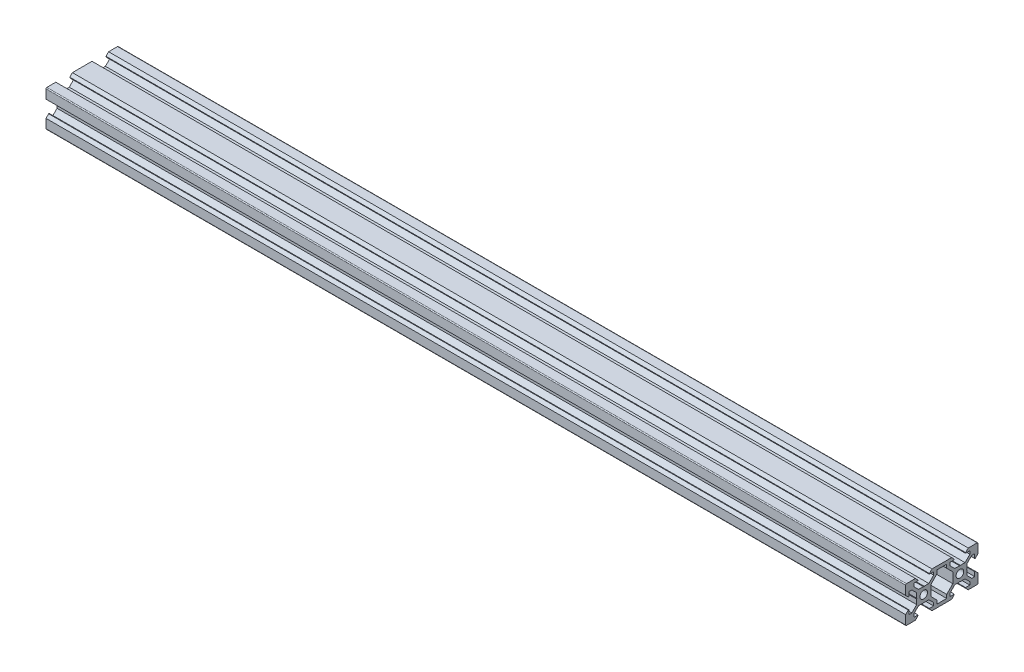
SolidWorks part; units mm, degrees
material "6061-T6 (SS)"
ref_plane "Top" through (0, 0, 0) normal (0, 0, 1) x (1, 0, 0)
ref_plane "Front" through (0, 0, 0) normal (0, 1, 0) x (1, 0, 0)
ref_plane "Right" through (0, 0, 0) normal (1, 0, 0) x (0, 0, -1)
sketch "Profile Sketch" plane through (0, 0, 0) normal (1, 0, 0) x (0, 0, -1)
  line L0 (5.42, 10) -> (-5.42, 10)
  line L1 (-4.5, 8.2) -> (-4.5, 6.56)
  line L2 (-4.5, 6.56) -> (-7.16, 3.9)
  line L3 (-7.16, 3.9) -> (-9.79, 3.9)
  line L4 (-9.79, 3.9) -> (-10, 3.69)
  line L5 (2.7, 8.2) -> (-2.7, 8.2)
  line L6 (-2.7, 8.2) -> (-2.7, 6.2387)
  line L7 (-2.7, 6.2387) -> (-6.1, 2.8387)
  line L8 (-6.1, 2.8387) -> (-6.1, -0.21)
  line L9 (-6.875, 8.545) -> (-6.875, 8.2)
  line L10 (-6.875, 8.2) -> (-4.5, 8.2)
  line L11 (-6.875, 8.545) -> (-5.42, 10)
  line L12 (0, -10) -> (0, 10) construction
  line L13 (-20, 0) -> (20, 0) construction
  line L14 (-10, -10) -> (-10, 10) construction
  line L15 (-6.875, -8.545) -> (-5.42, -10)
  line L16 (-6.875, -8.2) -> (-4.5, -8.2)
  line L17 (-6.875, -8.545) -> (-6.875, -8.2)
  line L18 (-2.7, -6.2387) -> (-6.1, -2.8387)
  line L19 (-2.7, -8.2) -> (-2.7, -6.2387)
  line L20 (2.7, -8.2) -> (-2.7, -8.2)
  line L21 (-7.16, -3.9) -> (-9.79, -3.9)
  line L22 (-4.5, -6.56) -> (-7.16, -3.9)
  line L23 (-4.5, -8.2) -> (-4.5, -6.56)
  line L24 (5.42, -10) -> (-5.42, -10)
  line L25 (-10, 0) -> (-20, 10) construction
  line L26 (-18.545, 3.125) -> (-18.2, 3.125)
  line L27 (-13.125, -8.545) -> (-13.125, -8.2)
  line L28 (-13.125, -8.2) -> (-15.5, -8.2)
  line L29 (-13.125, -8.545) -> (-14.58, -10)
  line L30 (-15.5, -8.2) -> (-15.5, -6.56)
  line L31 (-15.5, -6.56) -> (-12.84, -3.9)
  line L32 (-12.84, -3.9) -> (-10.21, -3.9)
  line L33 (-20, 4.58) -> (-20, 9.5)
  line L34 (-13.9, 2.8387) -> (-13.9, 0.21)
  line L35 (-16.56, 5.5) -> (-13.9, 2.8387)
  line L36 (-12.84, 3.9) -> (-10.21, 3.9)
  line L37 (-15.5, 6.56) -> (-12.84, 3.9)
  line L38 (-15.5, 8.2) -> (-15.5, 6.56)
  line L39 (-13.125, 8.545) -> (-14.58, 10)
  line L40 (-13.125, 8.2) -> (-15.5, 8.2)
  line L41 (-13.125, 8.545) -> (-13.125, 8.2)
  line L42 (-18.2, 3.125) -> (-18.2, 5.5)
  line L43 (-18.545, 3.125) -> (-20, 4.58)
  line L44 (-18.2, 5.5) -> (-16.56, 5.5)
  line L45 (-14.58, 10) -> (-19.5, 10)
  line L46 (-16.56, -5.5) -> (-13.9, -2.8387)
  line L47 (-14.58, -10) -> (-19.5, -10)
  line L48 (-18.2, -5.5) -> (-16.56, -5.5)
  line L49 (-18.545, -3.125) -> (-20, -4.58)
  line L50 (-18.2, -3.125) -> (-18.2, -5.5)
  line L51 (-20, -4.58) -> (-20, -9.5)
  line L52 (-18.545, -3.125) -> (-18.2, -3.125)
  line L53 (10, -10) -> (10, 10) construction
  line L54 (18.545, -3.125) -> (18.2, -3.125)
  line L55 (20, -4.58) -> (20, -9.5)
  line L56 (18.2, -3.125) -> (18.2, -5.5)
  line L57 (18.545, -3.125) -> (20, -4.58)
  line L58 (18.2, -5.5) -> (16.56, -5.5)
  line L59 (14.58, -10) -> (19.5, -10)
  line L60 (16.56, -5.5) -> (13.9, -2.8387)
  line L61 (14.58, 10) -> (19.5, 10)
  line L62 (18.2, 5.5) -> (16.56, 5.5)
  line L63 (18.545, 3.125) -> (20, 4.58)
  line L64 (18.2, 3.125) -> (18.2, 5.5)
  line L65 (13.125, 8.545) -> (13.125, 8.2)
  line L66 (13.125, 8.2) -> (15.5, 8.2)
  line L67 (13.125, 8.545) -> (14.58, 10)
  line L68 (15.5, 8.2) -> (15.5, 6.56)
  line L69 (15.5, 6.56) -> (12.84, 3.9)
  line L70 (12.84, 3.9) -> (10.21, 3.9)
  line L71 (16.56, 5.5) -> (13.9, 2.8387)
  line L72 (13.9, 2.8387) -> (13.9, 0.21)
  line L73 (20, 4.58) -> (20, 9.5)
  line L74 (12.84, -3.9) -> (10.21, -3.9)
  line L75 (15.5, -6.56) -> (12.84, -3.9)
  line L76 (15.5, -8.2) -> (15.5, -6.56)
  line L77 (13.125, -8.545) -> (14.58, -10)
  line L78 (13.125, -8.2) -> (15.5, -8.2)
  line L79 (13.125, -8.545) -> (13.125, -8.2)
  line L80 (18.545, 3.125) -> (18.2, 3.125)
  line L81 (4.5, -8.2) -> (4.5, -6.56)
  line L82 (4.5, -6.56) -> (7.16, -3.9)
  line L83 (7.16, -3.9) -> (9.79, -3.9)
  line L84 (2.7, -8.2) -> (2.7, -6.2387)
  line L85 (2.7, -6.2387) -> (6.1, -2.8387)
  line L86 (6.875, -8.545) -> (6.875, -8.2)
  line L87 (6.875, -8.2) -> (4.5, -8.2)
  line L88 (6.875, -8.545) -> (5.42, -10)
  line L89 (6.875, 8.545) -> (5.42, 10)
  line L90 (6.875, 8.2) -> (4.5, 8.2)
  line L91 (6.875, 8.545) -> (6.875, 8.2)
  line L92 (6.1, 2.8387) -> (6.1, -0.21)
  line L93 (2.7, 6.2387) -> (6.1, 2.8387)
  line L94 (2.7, 8.2) -> (2.7, 6.2387)
  line L95 (9.79, 3.9) -> (10, 3.69)
  line L96 (7.16, 3.9) -> (9.79, 3.9)
  line L97 (4.5, 6.56) -> (7.16, 3.9)
  line L98 (4.5, 8.2) -> (4.5, 6.56)
  line L99 (-10, 3.69) -> (-10.21, 3.9)
  line L100 (-10, -3.69) -> (-10.21, -3.9)
  line L101 (-9.79, -3.9) -> (-10, -3.69)
  line L102 (-13.9, -0.21) -> (-13.69, 0)
  line L103 (-13.69, 0) -> (-13.9, 0.21)
  line L104 (-13.9, -0.21) -> (-13.9, -2.8387)
  line L105 (-6.1, -0.21) -> (-6.31, 0)
  line L106 (-6.31, 0) -> (-6.1, -0.21)
  line L107 (-6.1, -0.21) -> (-6.1, -2.8387)
  line L108 (6.31, 0) -> (6.1, -0.21)
  line L109 (6.1, -0.21) -> (6.31, 0)
  line L110 (13.69, 0) -> (13.9, 0.21)
  line L111 (13.9, -0.21) -> (13.69, 0)
  line L112 (9.79, -3.9) -> (10, -3.69)
  line L113 (10, -3.69) -> (10.21, -3.9)
  line L114 (10, 3.69) -> (10.21, 3.9)
  line L115 (6.1, -0.21) -> (6.1, -2.8387)
  line L116 (13.9, -0.21) -> (13.9, -2.8387)
  line L118 (20, -10) -> (20, 10) construction
  line L119 (20, -10) -> (-20, -10) construction
  line L120 (-20, -10) -> (-20, 10) construction
  line L121 (20, 10) -> (-20, 10) construction
  line L122 (20, -10) -> (-20, 10) construction
  line L123 (-20, -10) -> (20, 10) construction
  circle A0 centre (-10, 0) radius 2.1
  arc A1 (-19.5, 10) -> (-20, 9.5) centre (-19.5, 9.5) ccw
  arc A2 (-19.5, -10) -> (-20, -9.5) centre (-19.5, -9.5) cw
  arc A3 (19.5, -10) -> (20, -9.5) centre (19.5, -9.5) ccw
  arc A4 (19.5, 10) -> (20, 9.5) centre (19.5, 9.5) cw
  circle A5 centre (10, 0) radius 2.1
  point P35 (-2.4957, 0)
  point P108 (0, -8.2)
  point P119 (0, 8.2)
  point P123 (2.4957, 0)
  point P131 (0, 0)
  point P143 (0, 0)
  dimension "D4" = 5.42
  dimension "D5" = 40
  dimension "D6" = 4.2
  dimension "D16" = 0.5
  dimension "D1" = 0.21
  dimension "D2" = 45
  dimension "D3" = 20
  dimension "D7" = 1.5
  dimension "D8" = 1.8
  dimension "D9" = 10
  dimension "D10" = 3.9
  dimension "D11" = 3.9
  dimension "D12" = 1.8
  dimension "D13" = 3.125
  dimension "D14" = 5.5
  dimension "D15" = 1.64
  dimension "D17" = 5.4
extrude "Profile Extrude" add sketch "Profile Sketch" along normal blind 475 contours A4 L61 L67 L65 L66 L68 L69 L70 L114 L95 L96 L97 L98 L90 L91 L89 L0 L11 L9 L10 L1 L2 L3 L4 L99 L36 L37 L38 L40 L41 L39 L45 A1 L33 L43 L26 L42 L44 L35 L34 L103 L102 L104 L46 L48 L50 L52 L49 L51 A2 L47 region at (0, 8.9563, -5.8313)
equation "\"M2x0.4_Close_Hole\"= 2.2"
equation "\"M2.5x0.45_Close_Hole\"= 2.7"
equation "\"M3x0.5_Close_Hole\"= 3.2"
equation "\"M4x0.7_Close_Hole\"= 4.3"
equation "\"M5x0.8_Close_Hole\"= 5.3"
equation "\"M6x1_Close_Hole\"= 6.3"
equation "\"M7x1_Close_Hole\"= 7.4"
equation "\"M8x1.25_Close_Hole\"= 8.4"
equation "\"M2x0.4_Tap_Hole_75\"= 1.6"
equation "\"M3x0.5_Tap_Hole_75\"= 2.5"
equation "\"M4x0.7_Tap_Hole_75\"= 3.3"
equation "\"M5x0.8_Tap_Hole_75\"= 4.2"
equation "\"M6x1_Tap_Hole_75\"= 5"
equation "\"M7x1_Tap_Hole_75\"= 6"
equation "\"M8x1.25_Tap_Hole_75\"= 6.8"
